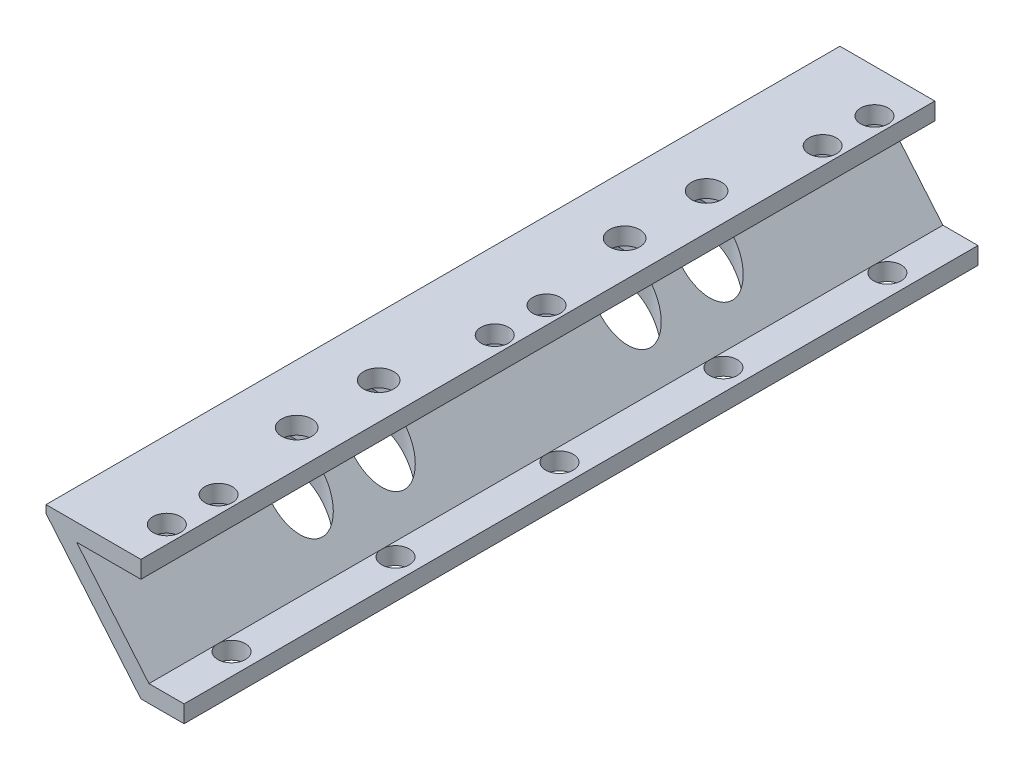
SolidWorks part; units mm, degrees
ref_plane "Front Plane" through (0, 0, 0) normal (0, 0, 1) x (1, 0, 0)
ref_plane "Top Plane" through (0, 0, 0) normal (0, 1, 0) x (1, 0, 0)
ref_plane "Right Plane" through (0, 0, 0) normal (1, 0, 0) x (0, 0, -1)
sketch "스케치1" plane through (0, 0, 0) normal (0, 0, 1) x (1, 0, 0)
  line L0 (0, 0) -> (50000, 0) construction
  line L1 (0, 0) -> (0, 50000) construction
  line L2 (0, 0) -> (-32139.3805, 38302.2222) construction
  line L3 (-3.1135, 6.8219) -> (-32142.494, 38309.0441) construction
  line L4 (76.8945, 2) -> (-49923.1055, 2) construction
  line L5 (-34.4266, 12) -> (-50034.4266, 12) construction
  line L6 (-40.9601, 14) -> (-50040.9601, 14) construction
  line L7 (5, -3.8411) -> (5, 49996.1589) construction
  line L8 (-10.0692, 12) -> (-10.0692, 27.1958) construction
  line L9 (-11, 12) -> (-11, 15.0198) construction
  line L10 (5, 0) -> (0, 0)
  line L11 (0, 0) -> (-10.0692, 12)
  line L12 (-10.0692, 12) -> (-11, 12)
  line L13 (-11, 12) -> (-11, 14)
  line L14 (-11, 14) -> (0, 14)
  line L15 (0, 14) -> (0, 12)
  line L16 (0, 12) -> (-7.4584, 12)
  line L17 (-7.4584, 12) -> (0.9326, 2)
  line L18 (0.9326, 2) -> (5, 2)
  line L19 (5, 2) -> (5, 0)
  line L20 (11.7496, 17.5) -> (-49988.2504, 17.5) construction
  dimension "D1" = 2
  dimension "D2" = 50
  dimension "D3" = 2
  dimension "D4" = 2
  dimension "D5" = 12
  dimension "D6" = 5
  dimension "D7" = 11
  dimension "D8" = 3.5
extrude "보스-돌출1" add sketch "스케치1" against normal blind 46 and the other way blind 46
sketch "스케치2" plane through (0, 14, 0) normal (0, 1, 0) x (1, 0, 0)
  line L0 (-1000, 0) -> (49000, 0) construction
  line L1 (-999.0674, 38) -> (49000.9326, 38) construction
  line L3 (-999.0674, -38) -> (49000.9326, -38) construction
  line L5 (-1000, -41) -> (49000, -41) construction
  line L7 (-1001.0794, -35) -> (48998.9206, -35) construction
  line L8 (-1000, -3) -> (49000, -3) construction
  line L10 (-1001.2074, 3) -> (48998.7926, 3) construction
  line L11 (-1000.9513, 35) -> (48999.0487, 35) construction
  line L12 (-1001.9757, 41) -> (48998.0243, 41) construction
  line L13 (-2, -988.1885) -> (-2, 49011.8115) construction
  line L14 (0, -46) -> (0, 46) construction
  circle A0 centre (-2, 41) radius 1.6
  circle A1 centre (-2, 35) radius 1.6
  circle A2 centre (-2, 3) radius 1.6
  circle A3 centre (-2, -3) radius 1.6
  circle A4 centre (-2, -35) radius 1.6
  circle A5 centre (-2, -41) radius 1.6
  dimension "D1" = 38
  dimension "D2" = 38
  dimension "D3" = 3
  dimension "D4" = 3
  dimension "D5" = 3
  dimension "D6" = 3
  dimension "D7" = 3
  dimension "D8" = 3
  dimension "D9" = 2
extrude "컷-돌출1" cut sketch "스케치2" against normal blind 5
sketch "스케치3" plane through (0, 2, 0) normal (0, 1, 0) x (1, 0, 0)
  line L0 (0, 0) -> (50000, 0) construction
  line L1 (11.4689, 38) -> (50011.4689, 38) construction
  line L2 (14.2858, -38) -> (50014.2858, -38) construction
  line L3 (20.4319, -19) -> (50020.4319, -19) construction
  line L4 (26.9621, 19) -> (50026.9621, 19) construction
  line L5 (2.5, 25.6087) -> (2.5, -49974.3913) construction
  line L6 (5, -46) -> (5, 46) construction
  circle A0 centre (2.5, 38) radius 1.6
  circle A1 centre (2.5, 19) radius 1.6
  circle A2 centre (2.5, 0) radius 1.6
  circle A3 centre (2.5, -19) radius 1.6
  circle A4 centre (2.5, -38) radius 1.6
  dimension "D1" = 2.5
  dimension "D2" = 38
  dimension "D3" = 38
  dimension "D4" = 19
  dimension "D5" = 19
extrude "컷-돌출2" cut sketch "스케치3" against normal blind 5
sketch "스케치4" plane through (0, 14, 0) normal (0, 1, 0) x (1, 0, 0)
  line L0 (-2, 35) -> (49998, 35) construction
  line L1 (-2, 3) -> (49998, 3) construction
  line L2 (-2, -3) -> (49998, -3) construction
  line L3 (-2, -35) -> (49998, -35) construction
  line L4 (-22.9795, -19) -> (49977.0205, -19) construction
  line L5 (-27.4381, 19) -> (49972.5619, 19) construction
  line L6 (-4.2, 49.3243) -> (-4.2, -49950.6757) construction
  line L7 (0, -46) -> (0, 46) construction
  line L8 (-27.1133, 23.75) -> (49972.8867, 23.75) construction
  line L9 (-27.0094, 14.25) -> (49972.9906, 14.25) construction
  line L10 (-22.9585, -14.25) -> (49977.0415, -14.25) construction
  line L11 (-20.3617, -23.75) -> (49979.6383, -23.75) construction
  circle A0 centre (-4.2, 23.75) radius 1.75
  circle A1 centre (-4.2, 14.25) radius 1.75
  circle A2 centre (-4.2, -14.25) radius 1.75
  circle A3 centre (-4.2, -23.75) radius 1.75
  dimension "D1" = 4.2
  dimension "D2" = 16
  dimension "D3" = 16
  dimension "D4" = 9.5
  dimension "D5" = 4.75
  dimension "D6" = 9.5
  dimension "D7" = 4.75
extrude "컷-돌출3" cut sketch "스케치4" against normal blind 10
sketch "스케치5" plane through (0, 12, 0) normal (0, -1, 0) x (1, 0, 0)
  circle A0 centre (-4.2, 23.75) radius 3
  circle A1 centre (-4.2, 14.25) radius 3
  circle A2 centre (-4.2, -14.25) radius 3
  circle A3 centre (-4.2, -23.75) radius 3
extrude "컷-돌출4" cut sketch "스케치5" along normal blind 20
sketch "스케치6" plane through (0, 0, 0) normal (-0.766, -0.6428, 0) x (0, 0, 1)
  line L1 (-56.6271, 32.3811) -> (51.966, 32.3811)
  line L2 (-56.6271, 32.3811) -> (-56.6271, 11.0592)
  line L3 (-56.6271, 11.0592) -> (51.966, 11.0592)
  line L4 (51.966, 32.3811) -> (51.966, 11.0592)
extrude "컷-돌출5" cut sketch "스케치6" along normal blind 20
